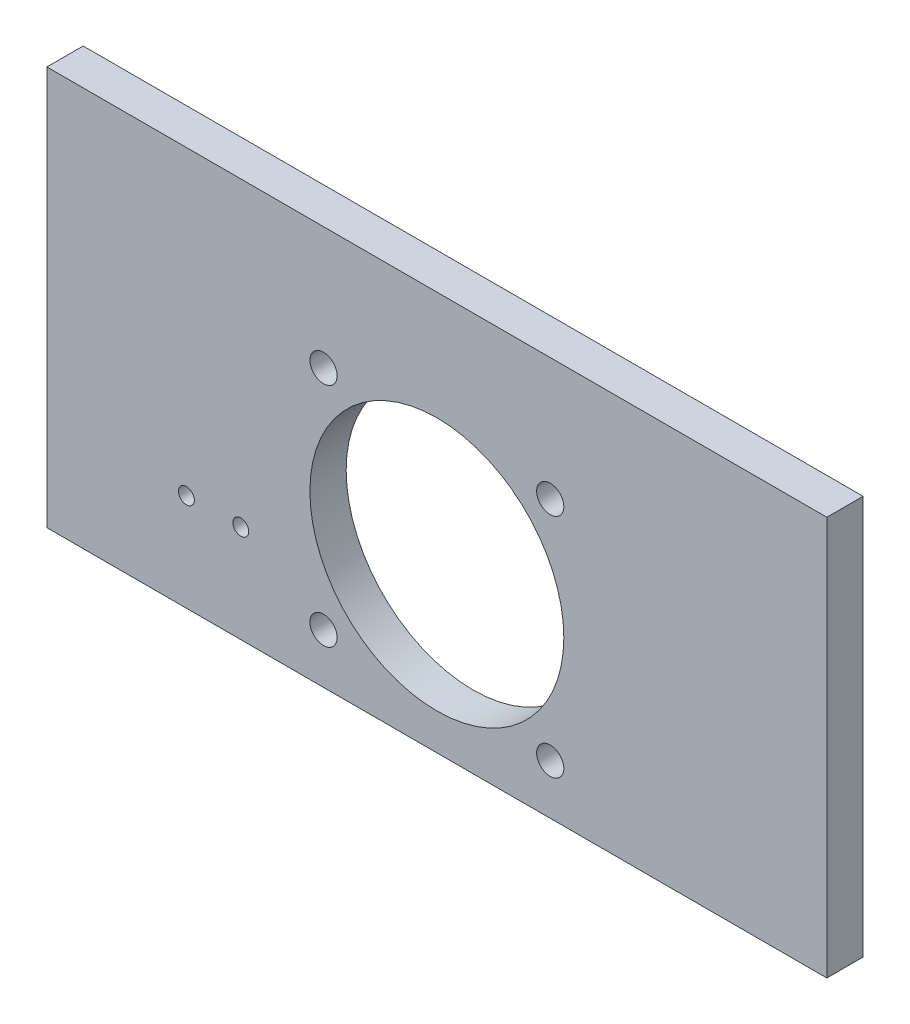
SolidWorks part; units mm, degrees
ref_plane "Płaszczyzna przednia" through (0, 0, 0) normal (0, 0, 1) x (1, 0, 0)
ref_plane "Płaszczyzna górna" through (0, 0, 0) normal (0, 1, 0) x (1, 0, 0)
ref_plane "Płaszczyzna prawa" through (0, 0, 0) normal (1, 0, 0) x (0, 0, -1)
sketch "Sketch1" plane through (0, 0, 0) normal (0, 0, 1) x (1, 0, 0)
  line L1 (0, 0) -> (86, 0)
  line L2 (0, 0) -> (0, 44)
  line L3 (0, 44) -> (86, 44)
  line L4 (86, 0) -> (86, 44)
  line L5 (0, 0) -> (86, 44) construction
  line L6 (0, 44) -> (86, 0) construction
  point P4 (43, 22)
  dimension "D1" = 86
  dimension "D2" = 44
extrude "Boss-Extrude1" add sketch "Sketch1" along normal blind 4
sketch "Sketch2" plane through (0, 0, 4) normal (0, 0, 1) x (1, 0, 0)
  line L0 (86, 44) -> (0, 44) construction
  line L1 (86, 0) -> (86, 44) construction
  circle A0 centre (43, 18) radius 14
  dimension "D1" = 28
  dimension "D2" = 26
  dimension "D3" = 43
extrude "Cut-Extrude1" cut sketch "Sketch2" against normal blind 4
sketch "Sketch3" plane through (0, 0, 4) normal (0, 0, 1) x (1, 0, 0)
  line L1 (28, 33) -> (58, 33) construction
  line L2 (28, 33) -> (28, 3) construction
  line L3 (28, 3) -> (58, 3) construction
  line L4 (58, 33) -> (58, 3) construction
  line L5 (28, 33) -> (58, 3) construction
  line L6 (28, 3) -> (58, 33) construction
  circle A0 centre (43, 18) radius 14 construction
  circle A1 centre (30.5, 30.5) radius 1.5
  circle A5 centre (55.5, 30.5) radius 1.5
  circle A6 centre (55.5, 5.5) radius 1.5
  circle A7 centre (30.5, 5.5) radius 1.5
  point P4 (43, 18)
  dimension "D4" = 3
  dimension "D5" = 2.5
  dimension "D6" = 2.5
  dimension "D1" = 30
  dimension "D2" = 15
  dimension "D3" = 15
  dimension "D7" = 4
extrude "Cut-Extrude3" cut sketch "Sketch3" against normal blind 4
hole_wizard "Ø1.0mm Dowel Hole1" positions "Sketch5" profile "Sketch6" hole size "Ø1.0" standard "ANSI Metric" end condition through all
sketch "Sketch5" plane through (0, 0, 4) normal (0, 0, 1) x (1, 0, 0)
  line L0 (0, 0) -> (86, 0) construction
  line L1 (0, 44) -> (0, 0) construction
  point P0 (15.38, 10.75)
  point P2 (21.38, 10.75)
  point P5 (0, 0)
  point P8 (15.2598, 10.75)
  dimension "D1" = 10.75
  dimension "D2" = 6
  dimension "D3" = 15.38
sketch "Sketch6" plane through (15.38, 10.75, 4) normal (1, 0, 0) x (0, -1, 0)
  line L0 (0, 0) -> (0, 4)
  line L1 (0, 4) -> (0.875, 4)
  line L2 (0.875, 4) -> (0.875, 0)
  line L5 (0.875, 0) -> (0, 0)
  line L11 (0, -6.35) -> (0, 107.95) construction
  dimension "Thru Hole Dia." = 1.75
  dimension "Thru Hole Depth" = 4
